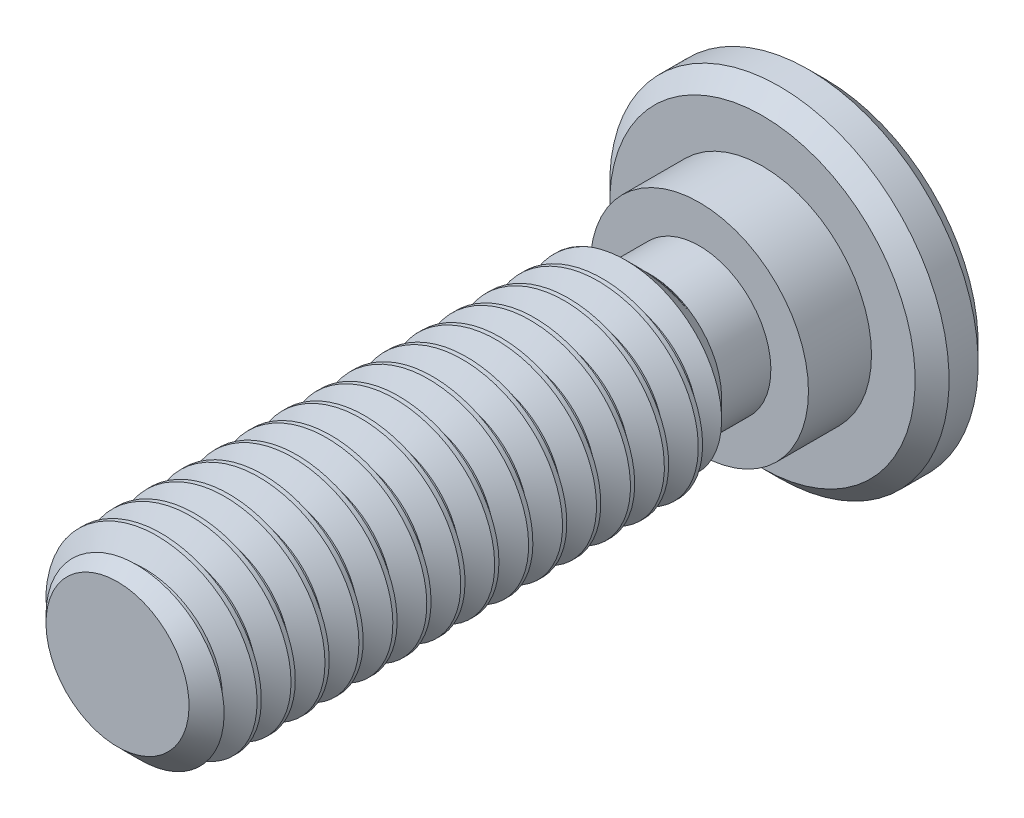
SolidWorks part; units mm, degrees
other "DetailItem1"
ref_plane "Front Plane" through (0, 0, 0) normal (0, 0, 1) x (1, 0, 0)
ref_plane "Top Plane" through (0, 0, 0) normal (0, 1, 0) x (1, 0, 0)
ref_plane "Right Plane" through (0, 0, 0) normal (1, 0, 0) x (0, 0, -1)
sketch "Sketch1" plane through (0, 0, 0) normal (1, 0, 0) x (0, 0, -1)
  line L0 (0, 0) -> (-13.3, 0) construction
  line L1 (0, 0) -> (1.3, 0) construction
  line L2 (1.3, 3.5) -> (1.3, -3.5) construction
  line L3 (-13.3, 2) -> (-13.3, -2) construction
  line L4 (0, 2.25) -> (0, -2.25) construction
  line L5 (-13.3, 2) -> (-12.6, 2) construction
  line L6 (1.3, 1.25) -> (1.3, -1.25) construction
  line L7 (0, 2.25) -> (-1.3, 2.25) construction
  line L8 (-1.3, 2.25) -> (-1.3, 1.475) construction
  line L9 (-1.3, 1.475) -> (-2.316, 1.475) construction
  line L10 (-2.316, 1.475) -> (-2.841, 2) construction
  point P2 (-10.85, -2)
  point P4 (-1.3, 0)
  point P8 (1.3, 0)
  point P11 (-13.3, 0)
  point P14 (0, 0)
  point P19 (1.3, 0)
  dimension "Thread Diameter" = 4
  dimension "Head Diameter" = 7
  dimension "Head Height" = 1.3
  dimension "Shoulder Diameter" = 4.5
  dimension "Shoulder Length" = 1.3
  dimension "Thread Pitch" = 0.7
  dimension "Drive Size" = 2.5
  dimension "D1" = 2.45
  dimension "D2" = 45
  dimension "Undercut Length" = 1.016
  dimension "D3" = 2.95
  dimension "Length" = 12
sketch "Sketch13" plane through (0, 0, 0) normal (1, 0, 0) x (0, 0, -1)
  line L0 (1.3, 3.5) -> (0, 3.5)
  line L1 (0, 3.5) -> (0, 2.25)
  line L3 (-13.3, 2) -> (-13.3, 0)
  line L4 (-13.3, 0) -> (1.3, 0)
  line L5 (1.3, 0) -> (1.3, 3.5)
  line L6 (-2.316, 1.475) -> (-2.841, 2) construction
  line L7 (-1.3, 1.475) -> (-2.316, 1.475) construction
  line L8 (-1.3, 2.25) -> (-1.3, 1.475) construction
  line L9 (0, 2.25) -> (-1.3, 2.25) construction
  line L10 (-2.316, 1.475) -> (-2.841, 2)
  line L11 (-1.3, 1.475) -> (-2.316, 1.475)
  line L12 (-1.3, 2.25) -> (-1.3, 1.475)
  line L13 (0, 2.25) -> (-1.3, 2.25)
  line L14 (-2.841, 2) -> (-13.3, 2)
revolve "Revolve1" add sketch "Sketch13" angle 360 about L4
sketch "Sketch2" plane through (0, 0, 13.3) normal (0, 0, 1) x (1, 0, 0)
  circle A2 centre (0, 0) radius 2
chamfer "Chamfer2" distance 0.525 angle 45 1 edges at (0, -2, 13.3)
sketch "Sketch3" plane through (0, 0, 0) normal (1, 0, 0) x (0, 0, -1)
  line L0 (-13.2563, 2.0758) -> (-13.9563, 2.0758) construction
  line L1 (-13.9563, 2.0758) -> (-13.6063, 1.4696) construction
  line L2 (-13.6063, 1.4696) -> (-13.2563, 2.0758) construction
  line L4 (-13.3, 2) -> (-13.9125, 2) construction
  line L5 (-13.6063, 2.0758) -> (-13.6063, 2) construction
  line L6 (-13.9344, 2.0379) -> (-13.2781, 2.0379)
  line L7 (-13.2781, 2.0379) -> (-13.9344, 2.0379) construction
  line L8 (-13.5625, 1.5453) -> (-13.65, 1.5453) construction
  line L9 (-13.6063, 1.5453) -> (-13.6063, 1.4696) construction
  line L10 (-13.2781, 2.0379) -> (-13.5625, 1.5453)
  line L11 (-13.5625, 1.5453) -> (-13.65, 1.5453)
  line L12 (-13.65, 1.5453) -> (-13.9344, 2.0379)
  point P16 (-13.6063, 2.0379)
  dimension "D1" = 0.7
  dimension "D2" = 0.0875
sketch "Sketch7" plane through (0, 0, -1.3) normal (0, 0, -1) x (-1, 0, 0)
  line L1 (0, 1.4434) -> (-1.25, 0.7217)
  line L2 (-1.25, 0.7217) -> (-1.25, -0.7217)
  line L3 (-1.25, -0.7217) -> (0, -1.4434)
  line L4 (0, -1.4434) -> (1.25, -0.7217)
  line L5 (1.25, -0.7217) -> (1.25, 0.7217)
  line L6 (1.25, 0.7217) -> (0, 1.4434)
  circle A0 centre (0, 0) radius 1.25 construction
extrude "Cut-Extrude1" cut sketch "Sketch7" against normal blind 1.875
chamfer "Chamfer1" distance 0.35 angle 45 2 edges at (0, -3.5, -1.3) (0, -3.5, 0)
sketch "Sketch8" plane through (0, 0, -1.3) normal (0, 0, -1) x (-1, 0, 0)
  circle A0 centre (0, 0) radius 1.4434
extrude "Cut-Extrude2" cut sketch "Sketch8" against normal through all draft 45
curve "Helix/Spiral1" pitch 0.7 height 11.9 radius 2 centre (0, 0, 13.3) axis (0, 0, -1) start towards (0, 1, 0) parameters "pitch"=0.7
sweep "Cut-Sweep1" cut profiles "Sketch3" path "Helix/Spiral1"
equation "\"D3@Helix/Spiral1\"=\"Length@Sketch1\"-.1"
equation "\"D1@Cut-Extrude1\" = \"Drive Size@Sketch1\" * .75"
equation "\"D1@Chamfer1\" = \"Head Diameter@Sketch1\" * .05"
equation "\"D1@Chamfer2\"=\"pitch@Helix/Spiral1\"*.750"
equation "\"D1@Sketch3\" = \"Thread Pitch@Sketch1\""
equation "\"D2@Sketch3\"=\"D1@Sketch3\"/ 1/8"
equation "\"pitch@Helix/Spiral1\" = \"Thread Pitch@Sketch1\""
equation "\"D1@Sketch1\" = \"Thread Pitch@Sketch1\" * 3.5"
equation "\"D3@Sketch1\"=\"Thread Diameter@Sketch1\"-(\"Thread Pitch@Sketch1\"*1.5)"
